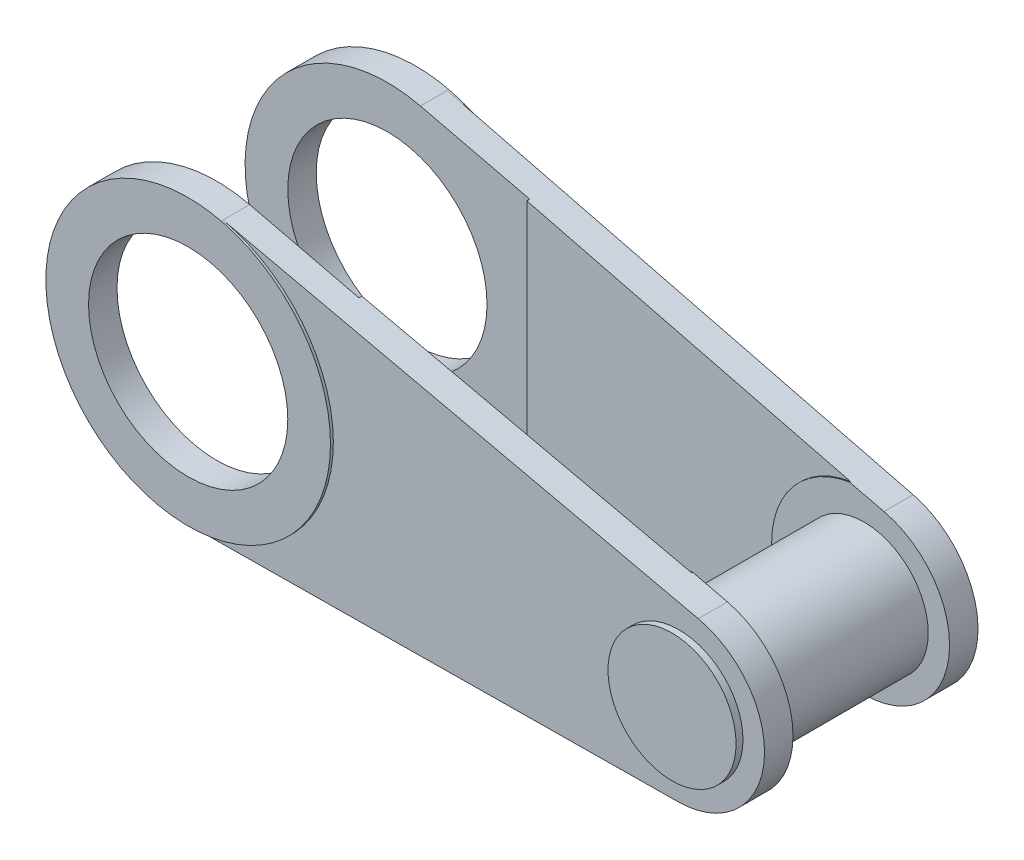
SolidWorks part; units mm, degrees
ref_plane "前基準面" through (0, 0, 0) normal (0, 0, 1) x (1, 0, 0)
ref_plane "上基準面" through (0, 0, 0) normal (0, 1, 0) x (1, 0, 0)
ref_plane "右基準面" through (0, 0, 0) normal (1, 0, 0) x (0, 0, -1)
sketch "草圖1" plane through (0, 0, 0) normal (0, 1, 0) x (1, 0, 0)
  line L0 (0, -8) -> (50, -7.5)
  line L1 (50, -7.5) -> (50, 7.5)
  line L2 (50, 7.5) -> (0, 8)
  line L3 (0, 8) -> (0, -8)
  point P3 (0, 0)
  dimension "D1" = 15
  dimension "D2" = 16
  dimension "D3" = 50
extrude "填料-伸長1" add sketch "草圖1" along normal blind 60
sketch "草圖2" plane through (0, 0, 0) normal (0, 0, 1) x (1, 0, 0)
  line L0 (0, 0) -> (0, 60)
  line L1 (0, 60) -> (50, 60)
  line L2 (50, 60) -> (50, 0)
  line L3 (0, 0) -> (50, 0) construction
  line L4 (50, 0) -> (44, 0)
  line L5 (0, 0) -> (10, 0)
  line L6 (12.3208, 19.727) -> (45.3925, 11.8362)
  arc A2 (10, 0) -> (12.3208, 19.727) centre (10, 10) cw
  arc A3 (44, 0) -> (45.3925, 11.8362) centre (44, 6) ccw
  circle A4 centre (10, 10) radius 7
  circle A5 centre (44, 6) radius 4.5
  dimension "D1" = 10
  dimension "D2" = 6
  dimension "D3" = 14
  dimension "D4" = 9
extrude "除料-伸長2" cut sketch "草圖2" against normal mid plane 50 contours A4 | L5 A2 L0 | A3 L2 L1 L0 A2 L6 | A5 | A3 L4 L2 region at (48.6598, 1.3402, 0) region at (25.8087, 37.8416, 0) region at (2.2337, 2.2337, 0) region at (10, 10, 0) region at (44, 6, 0)
shell "薄殼2" thickness 2 removed face at (5.6145, 10.5159, 0) removed face at (28.8567, 15.7816, 0) removed face at (27, 0, 0) removed face at (47.3276, 5.6085, 0)
sketch "草圖5" plane through (0, 0, 0) normal (0, 0, 1) x (1, 0, 0)
  circle A0 centre (10, 10) radius 10
  circle A2 centre (10, 10) radius 7
  dimension "D1" = 20
  dimension "D2" = 14
extrude "填料-伸長2" add sketch "草圖5" along normal mid plane 16
sketch "草圖7" plane through (0, 0, 0) normal (0, 1, 0) x (1, 0, 0)
  line L1 (50.5, 5.5) -> (50.5, -5.5)
  line L3 (37.5, -5.5) -> (37.5, 5.5)
  line L7 (37.5, 5.6249) -> (37.5, -5.6249) construction
  line L8 (37.5, 5.5) -> (50.5, 5.5)
  line L9 (37.5, -5.5) -> (50.5, -5.5)
  line L14 (37.5, 0) -> (50.5, 0) construction
  line L16 (45.3925, 7.5461) -> (45.3925, -7.5461) construction
  point P6 (45.3925, 0)
  dimension "D1" = 11
  dimension "D3" = 13
extrude "除料-伸長7" cut sketch "草圖7" along normal through all
sketch "草圖6" plane through (0, 0, 0) normal (0, 0, 1) x (1, 0, 0)
  circle A0 centre (44, 6) radius 4.5
  dimension "D2" = 9
extrude "填料-伸長3" add sketch "草圖6" along normal mid plane 16
sketch "草圖8" plane through (0, 0, 0) normal (0, 1, 0) x (1, 0, 0)
  line L1 (0, 6) -> (20, 6)
  line L2 (0, 6) -> (0, -6)
  line L3 (0, -6) -> (20, -6)
  line L4 (20, 6) -> (20, -6)
  line L5 (0, 0) -> (20, 0) construction
  line L6 (10, 8) -> (10, -8) construction
  point P4 (10, 0)
  dimension "D1" = 12
  dimension "D2" = 20
extrude "除料-伸長8" cut sketch "草圖8" along normal through all
